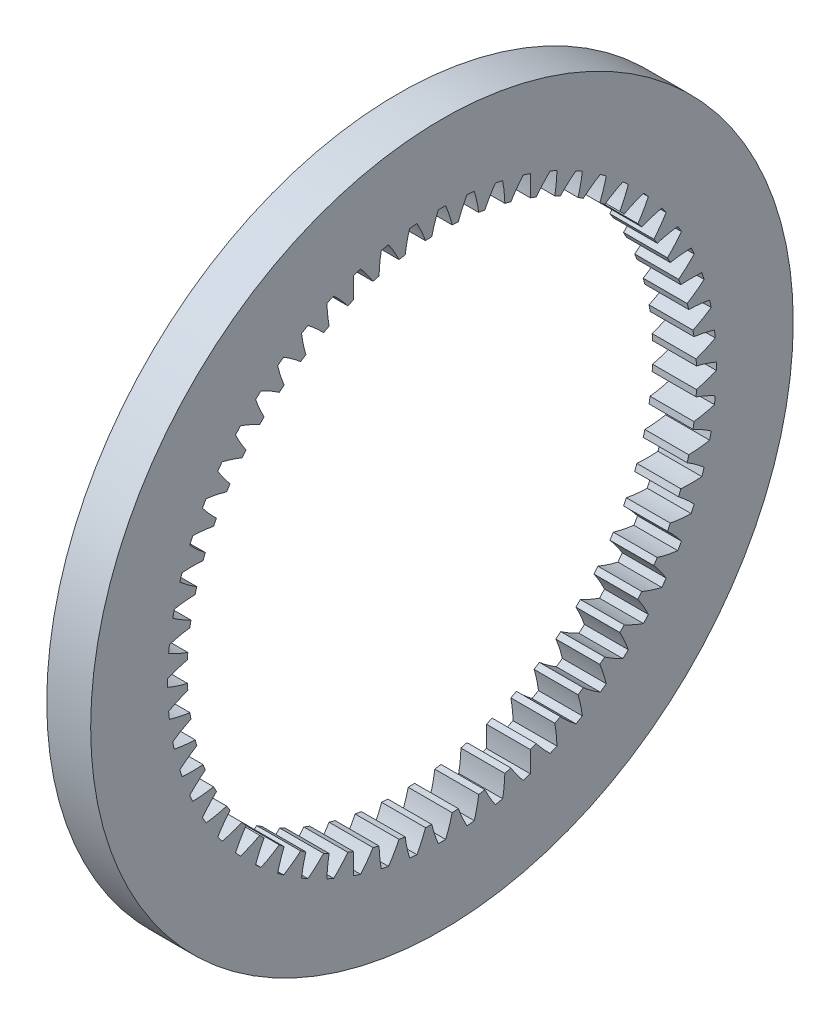
SolidWorks part; units mm, degrees
ref_plane "Plane1" through (0, 0, 0) normal (0, 0, 1) x (1, 0, 0)
ref_plane "Plane2" through (0, 0, 0) normal (0, 1, 0) x (1, 0, 0)
ref_plane "Plane3" through (0, 0, 0) normal (1, 0, 0) x (0, 0, -1)
sketch "HoldingSke" plane through (0, 0, 0) normal (0, 1, 0) x (1, 0, 0)
  line L0 (0, 0) -> (0.5, -0.866)
  line L1 (-15, 0) -> (100, 0) construction
  line L2 (0, 0) -> (-2.1039, 2.3779)
  line L3 (0, 0) -> (-11.863, 4.5341)
  line L4 (0, 0) -> (4.318, 7.479)
  line L5 (0, 0) -> (-23.7986, -8.8762)
  line L6 (0, 0) -> (-10.5278, -7.1032)
  line L7 (-2.1039, 2.3779) -> (3.3635, 27.1825)
  line L8 (-76.2, 3.3779) -> (-54.61, 3.3779)
  line L9 (-67.7845, 28.3722) -> (-49.3413, 33.142)
  line L10 (-76.2, 71.12) -> (104.1128, 71.12)
  line L11 (0, 0) -> (-5, 0)
  line L12 (-76.2, 101.6) -> (-76.162, 101.6)
  line L13 (24.9733, 27.94) -> (52.9518, 28.4284)
  line L14 (24.9733, 27.94) -> (24.9743, 27.94)
  line L15 (24.9733, 27.94) -> (100.4006, 29.5858)
  circle A0 centre (0, 0) radius 40
  circle A1 centre (0, 0) radius 12.7
  circle A2 centre (0, 0) radius 12.7
  dimension "Num_teeth" = 60
  dimension "Pitch_radius" = 180.3128
  dimension "Width" = 5
  dimension "Diameter" = 80
sketch "BasProSke" plane through (0, 0, 0) normal (0, 1, 0) x (1, 0, 0)
  line L0 (-10, 0) -> (60, 0) construction
  line L1 (0, 29) -> (0, 40)
  line L2 (0, 29) -> (5, 29)
  line L3 (5, 29) -> (5, 40)
  line L4 (5, 40) -> (0, 40)
  dimension "Thickness" = 5
  dimension "Diameter" = 80
revolve "Base-Revolve" add sketch "BasProSke" angle 360 about L0
sketch "TooCutSke" plane through (0, 0, 0) normal (1, 0, 0) x (0, 0, -1)
  line L3 (0.8803, 29.9871) -> (0.8803, 53.6633) construction
  line L4 (0, 0) -> (0, 59.563) construction
  line L5 (0, 0) -> (-3.576, 68.2339) construction
  line L6 (-13.4241, 25.4723) -> (36.4229, 28.0847) construction
  circle A0 centre (0, 0) radius 30 construction
  circle A1 centre (0, 0) radius 31.251 construction
  circle A2 centre (0, 0) radius 26.14 construction
  circle A3 centre (0, 0) radius 28.9746 construction
  arc A4 (1.1669, 28.9511) -> (0.4193, 31.2482) centre (-13.4241, 25.4723) ccw
  arc A5 (1.1669, 28.9511) -> (-1.1669, 28.9511) centre (0, 0) ccw
  arc A6 (0.4193, 31.2482) -> (-0.4193, 31.2482) centre (0, 0) ccw
  arc A7 (-0.4193, 31.2482) -> (-1.1669, 28.9511) centre (13.4241, 25.4723) ccw
extrude "ToothCut" cut sketch "TooCutSke" along normal through all
fillet "Breaks" [suppressed] radius 0.1
fillet "RootFillets" [suppressed] radius 0.251
pattern_circular "TeethCuts" count 60 every 6 about axis through (-10, 0, 0) along (1, 0, 0) of "RootFillets", "Breaks", "ToothCut"
equation "' \"Module@HoldingSke\" = 6.35"
equation "' \"Num_teeth@HoldingSke\" = 24"
equation "' \"Ap@HoldingSke\" =  14.5"
equation "' \"Ap@HoldingSke\" = 14.5"
equation "' \"Width@HoldingSke\" = 12"
equation "' \"Diameter@HoldingSke\" = 8 * 25.4"
equation "' \"Show_teeth@HoldingSke\" = 100"
equation "' \"Backlash@HoldingSke\" = 0.009 * 25.4"
equation "' \"Addendum_fac@HoldingSke\" = 1.0"
equation "' \"Dedendum_fac@HoldingSke\" = 1.25"
equation "' \"Dedendum_add@HoldingSke\" = 0.00005 * 25.4"
equation "' \"Clearance_fac@HoldingSke\" = 0.25"
equation "\"Pitch@HoldingSke\" = 1 / \"Module@HoldingSke\" "
equation "\"Overcut_dia@TooCutSke\" = (\"Num_teeth@HoldingSke\" - 2 * \"Addendum_fac@HoldingSke\") / \"Pitch@HoldingSke\" - 0.002 * 25.4"
equation "\"Pitch_dia@TooCutSke\" = \"Num_teeth@HoldingSke\" / \"Pitch@HoldingSke\""
equation "\"Base_dia@TooCutSke\" = \"Num_teeth@HoldingSke\" / \"Pitch@HoldingSke\" * cos((\"Ap@HoldingSke\"  * 3.14159265 / 180)) * 0.90"
equation "\"Root_dia@TooCutSke\" = \"Num_teeth@HoldingSke\"  / \"Pitch@HoldingSke\" + 2 *  \"Dedendum_fac@HoldingSke\"/ \"Pitch@HoldingSke\" + \"Dedendum_add@HoldingSke\" * 2"
equation "\"Half_ang@TooCutSke\" = 180 / \"Num_teeth@HoldingSke\""
equation "\"Half_CT@TooCutSke\" = \"Num_teeth@HoldingSke\" / \"Pitch@HoldingSke\" * sin((3.14159265 / 2 / \"Num_teeth@HoldingSke\")) / 2 + 10 * \"Backlash@HoldingSke\" / 4"
equation "\"Flank_rad@TooCutSke\" = \"Num_teeth@HoldingSke\" / \"Pitch@HoldingSke\" / 4"
equation "\"Radius@RootFillets\"= \"Clearance_fac@HoldingSke\" / \"Pitch@HoldingSke\" + \"Dedendum_add@HoldingSke\""
equation "\"Break_rad@Breaks\" = 0.02 / \"Pitch@HoldingSke\" * 5"
equation "\"Num_teeth@TeethCuts\" = int( \"Show_teeth@HoldingSke\" ) + 1"
equation "\"Num_teeth@TeethCuts\" = ((sgn( \"Num_teeth@TeethCuts\" - \"Num_teeth@HoldingSke\" )-1)*( \"Num_teeth@TeethCuts\" - \"Num_teeth@HoldingSke\" ))/-2+ \"Num_teeth@HoldingSke\""
equation "\"Num_teeth@TeethCuts\" = ((sgn( \"Num_teeth@TeethCuts\" - 2.0)+1)*( \"Num_teeth@TeethCuts\" - 2.0))/2 +2.0"
equation "\"Angle@TeethCuts\" = 360.0 / \"Num_teeth@HoldingSke\""
equation "\"Diameter@BasProSke\" = \"Num_teeth@HoldingSke\"  / \"Pitch@HoldingSke\" + 2 *  \"Dedendum_fac@HoldingSke\"/ \"Pitch@HoldingSke\" + \"Dedendum_add@HoldingSke\" * 2 + 0.002 * 25.4"
equation "\"Diameter@BasProSke\" = ((sgn( \"Diameter@BasProSke\"  - \"Diameter@HoldingSke\" )+1)*( \"Diameter@BasProSke\"  - \"Diameter@HoldingSke\" ))/2 + \"Diameter@HoldingSke\""
equation "\"Inside_diameter@BasProSke\" =  (\"Num_teeth@HoldingSke\" - 2 * \"Addendum_fac@HoldingSke\") / \"Pitch@HoldingSke\" "
equation "\"Thickness@BasProSke\"  = \"Width@HoldingSke\""
